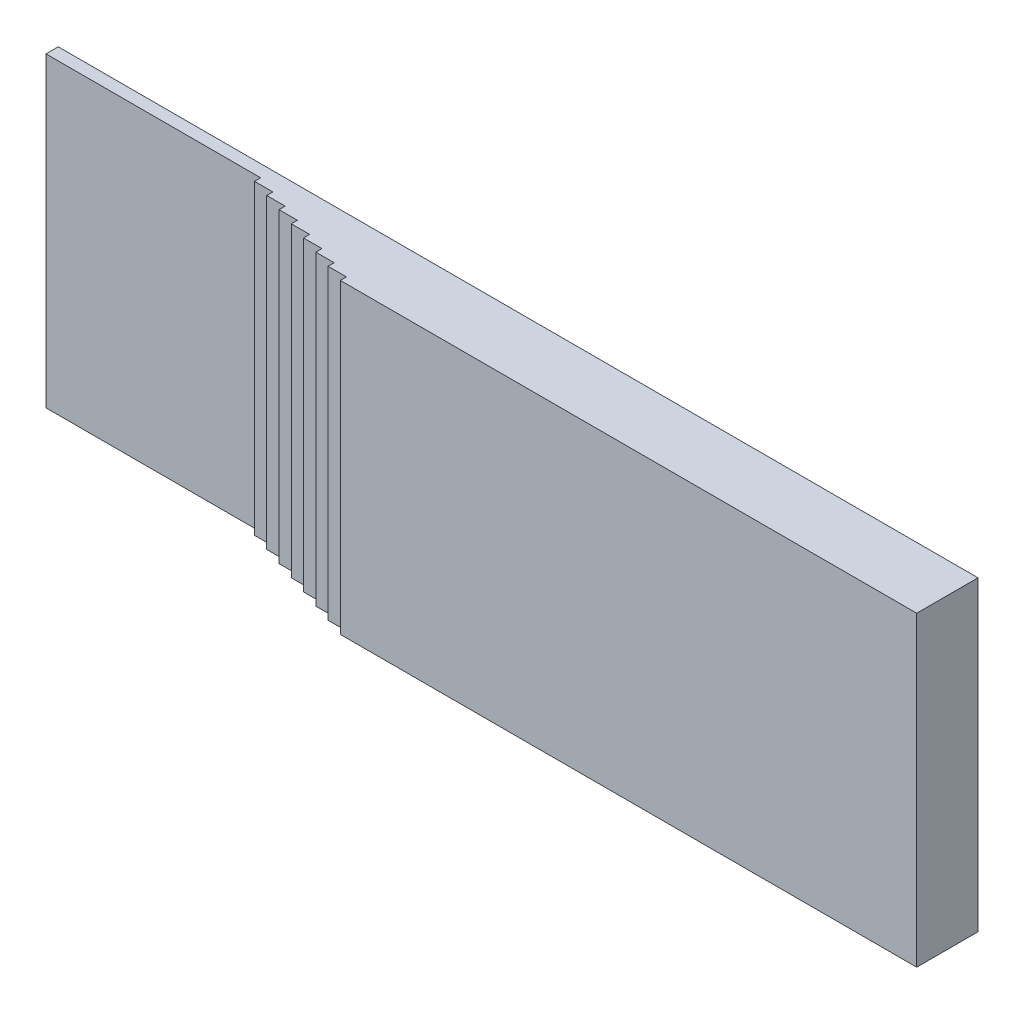
SolidWorks part; units mm, degrees
ref_plane "Front Plane" through (0, 0, 0) normal (0, 0, 1) x (1, 0, 0)
ref_plane "Top Plane" through (0, 0, 0) normal (0, 1, 0) x (1, 0, 0)
ref_plane "Right Plane" through (0, 0, 0) normal (1, 0, 0) x (0, 0, -1)
sketch "Sketch3" plane through (0, 0, 0) normal (0, 0, 1) x (1, 0, 0)
  line L1 (-2500, 2500) -> (12500, 2500)
  line L2 (-2500, 2500) -> (-2500, -2500)
  line L3 (-2500, -2500) -> (12500, -2500)
  line L4 (12500, 2500) -> (12500, -2500)
  line L5 (-2500, 2500) -> (12500, -2500) construction
  line L6 (-2500, -2500) -> (12500, 2500) construction
  point P0 (5000, 0)
  dimension "D1" = 15000
  dimension "D2" = 5000
  dimension "D3" = 5000
extrude "Boss-Extrude1" add sketch "Sketch3" along normal blind 200
sketch "Sketch4" plane through (0, 0, 200) normal (0, 0, 1) x (1, 0, 0)
  line L0 (-2500, -2500) -> (12500, -2500) construction
  line L1 (1000, -2500) -> (1300, -2500)
  line L2 (1000, -2500) -> (1000, 2500)
  line L3 (1000, 2500) -> (1300, 2500)
  line L4 (1300, -2500) -> (1300, 2500)
  line L5 (12500, 2500) -> (-2500, 2500) construction
  line L6 (1300, -2500) -> (1300, 2500)
  line L7 (1300, -2500) -> (1600, -2500)
  line L8 (1600, -2500) -> (1600, 2500)
  line L9 (1300, 2500) -> (1600, 2500)
  line L10 (1600, -2500) -> (1600, 2500)
  line L11 (1600, -2500) -> (1900, -2500)
  line L12 (1900, -2500) -> (1900, 2500)
  line L13 (1600, 2500) -> (1900, 2500)
  line L14 (1900, -2500) -> (1900, 2500)
  line L15 (1900, -2500) -> (2200, -2500)
  line L16 (2200, -2500) -> (2200, 2500)
  line L17 (1900, 2500) -> (2200, 2500)
  line L18 (2200, -2500) -> (2200, 2500)
  line L19 (2200, -2500) -> (2500, -2500)
  line L20 (2500, -2500) -> (2500, 2500)
  line L21 (2200, 2500) -> (2500, 2500)
  line L22 (2500, -2500) -> (2500, 2500)
  line L23 (2500, -2500) -> (2800, -2500)
  line L24 (2800, -2500) -> (2800, 2500)
  line L25 (2500, 2500) -> (2800, 2500)
  line L26 (2800, -2500) -> (2800, 2500)
  line L27 (2800, -2500) -> (3100, -2500)
  line L28 (3100, -2500) -> (3100, 2500)
  line L29 (2800, 2500) -> (3100, 2500)
  line L30 (3100, -2500) -> (3100, 2500)
  line L31 (3100, -2500) -> (3400, -2500)
  line L32 (3400, -2500) -> (3400, 2500)
  line L33 (3100, 2500) -> (3400, 2500)
  line M6 (12500, 2500) -> (-2500, 2500)
  line M8 (-2500, -2500) -> (12500, -2500)
  dimension "D1" = 1000
  dimension "D2" = 300
  dimension "D3" = 8
extrude "Step1" add sketch "Sketch4" along normal blind 100 contours L4 L2 M8 M6 region at (1150, 0, 200)
extrude "Step2" add sketch "Sketch4<4>" along normal blind 200 contours L8 L4 M8 M6 region at (1450, 0, 200)
sketch "Sketch4<4>" plane through (0, 0, 200) normal (0, 0, 1) x (1, 0, 0) same geometry as "Sketch4"
extrude "Step3" add sketch "Sketch4<5>" along normal blind 300 contours L12 L8 M8 M6 region at (1750, 0, 200)
sketch "Sketch4<5>" plane through (0, 0, 200) normal (0, 0, 1) x (1, 0, 0) same geometry as "Sketch4"
extrude "Step4" add sketch "Sketch4<6>" along normal blind 400 contours L16 L12 M8 M6 region at (2050, 0, 200)
sketch "Sketch4<6>" plane through (0, 0, 200) normal (0, 0, 1) x (1, 0, 0) same geometry as "Sketch4"
extrude "Step5" add sketch "Sketch4<7>" along normal blind 500 contours L20 L16 M8 M6 region at (2350, 0, 200)
sketch "Sketch4<7>" plane through (0, 0, 200) normal (0, 0, 1) x (1, 0, 0) same geometry as "Sketch4"
extrude "Step6" add sketch "Sketch4<8>" along normal blind 600 contours L24 L20 M8 M6 region at (2650, 0, 200)
sketch "Sketch4<8>" plane through (0, 0, 200) normal (0, 0, 1) x (1, 0, 0) same geometry as "Sketch4"
extrude "Step7" add sketch "Sketch4<9>" along normal blind 700 contours L28 L24 M8 M6 region at (2950, 0, 200)
sketch "Sketch4<9>" plane through (0, 0, 200) normal (0, 0, 1) x (1, 0, 0) same geometry as "Sketch4"
extrude "Step8" add sketch "Sketch4<10>" along normal blind 800 contours L32 L28 M8 M6 region at (3250, 0, 200)
sketch "Sketch4<10>" plane through (0, 0, 200) normal (0, 0, 1) x (1, 0, 0) same geometry as "Sketch4"
sketch "Sketch8" plane through (0, 0, 200) normal (0, 0, 1) x (1, 0, 0)
  line L4 (12500, 2500) -> (3400, 2500)
  line L5 (3400, 2500) -> (3400, -2500)
  line L6 (3400, -2500) -> (12500, -2500)
  line L7 (12500, -2500) -> (12500, 2500)
  line L8 (12500, 2500) -> (3400, 2500)
  line L10 (3400, -2500) -> (12500, -2500)
  line L11 (12500, -2500) -> (12500, 2500)
  line L12 (3400, 2500) -> (3400, -2500)
  dimension "D1" = 0
extrude "Step9" add sketch "Sketch8" along direction (0, 0, 1) on the side of the normal blind 800
